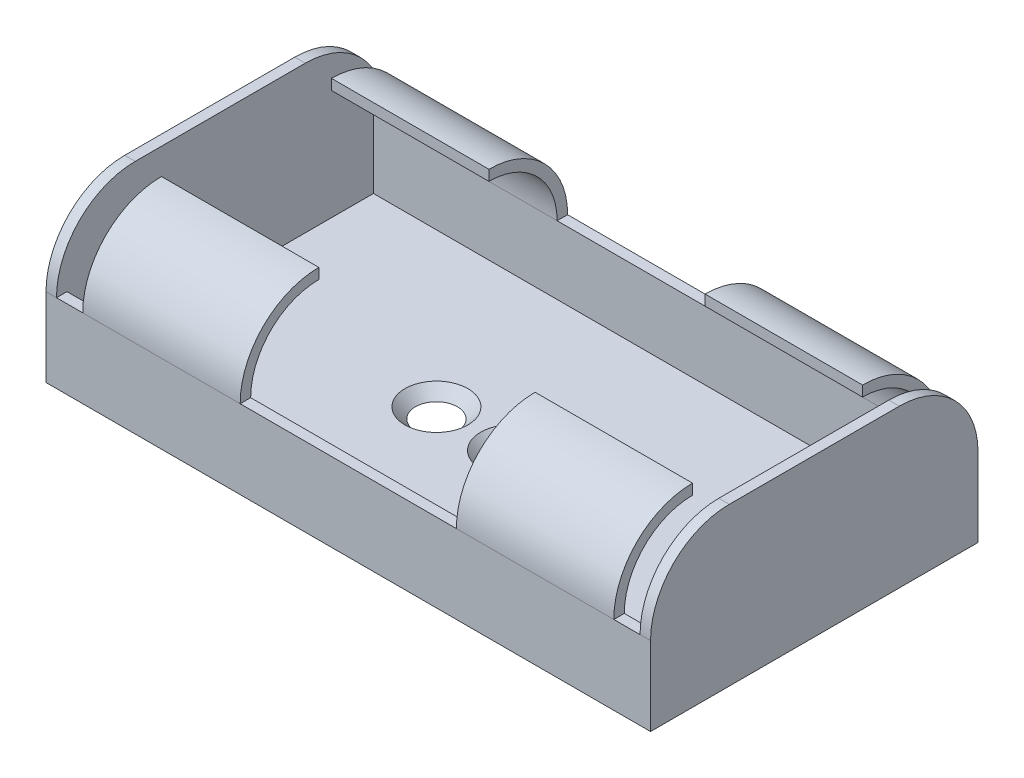
SolidWorks part; units mm, degrees
ref_plane "Front Plane" through (0, 0, 0) normal (0, 0, 1) x (1, 0, 0)
ref_plane "Top Plane" through (0, 0, 0) normal (0, 1, 0) x (1, 0, 0)
ref_plane "Right Plane" through (0, 0, 0) normal (1, 0, 0) x (0, 0, -1)
sketch "Sketch1" plane through (0, 0, 0) normal (0, 1, 0) x (1, 0, 0)
  line L1 (-28.8, 15.6) -> (28.8, 15.6)
  line L2 (-28.8, 15.6) -> (-28.8, -15.6)
  line L3 (-28.8, -15.6) -> (28.8, -15.6)
  line L4 (28.8, 15.6) -> (28.8, -15.6)
  line L5 (-28.8, 15.6) -> (28.8, -15.6) construction
  line L6 (-28.8, -15.6) -> (28.8, 15.6) construction
  point P0 (0, 0)
  dimension "D1" = 57.6
  dimension "D2" = 31.2
extrude "Boss-Extrude1" add sketch "Sketch1" along normal blind 15
fillet "Fillet1" radius 7.5 2 edges at (0, 15, -15.6) (0, 15, 15.6)
shell "Shell1" thickness 1 removed face at (0, 15, 0)
sketch "Sketch4" plane through (0, 0, 15.6) normal (0, 0, 1) x (1, 0, 0)
  line L0 (28.8, 7.5) -> (-28.8, 7.5) construction
  line L1 (-27.8, 15) -> (-25.3, 15)
  line L2 (-27.8, 15) -> (-27.8, 7.5)
  line L3 (-27.8, 7.5) -> (-25.3, 7.5)
  line L4 (-25.3, 15) -> (-25.3, 7.5)
  line L5 (-27.8, 15) -> (27.8, 15) construction
  line L6 (-10.3, 15) -> (10.3, 15)
  line L7 (-10.3, 15) -> (-10.3, 7.5)
  line L8 (-10.3, 7.5) -> (10.3, 7.5)
  line L10 (0, 0) -> (0, 7.5) construction
  line L11 (-28.8, 0) -> (28.8, 0) construction
  line L12 (10.3, 15) -> (10.3, 7.5)
  line L13 (25.3, 15) -> (25.3, 7.5)
  line L14 (27.8, 7.5) -> (25.3, 7.5)
  line L15 (27.8, 15) -> (27.8, 7.5)
  line L16 (27.8, 15) -> (25.3, 15)
  dimension "D1" = 2.5
  dimension "D2" = 15
extrude "Cut-Extrude1" cut sketch "Sketch4" against normal through all
sketch "Sketch5" plane through (0, 1, 0) normal (0, 1, 0) x (1, 0, 0)
  circle A0 centre (0, 0) radius 1.4
  circle A1 centre (7.2, 0) radius 1.4
  circle A2 centre (-7.2, 0) radius 1.4
  dimension "D1" = 2.8
  dimension "D2" = 7.2
  dimension "D3" = 7.2
extrude "Cut-Extrude2" cut sketch "Sketch5" against normal blind 15
hole_wizard "M3 Tapped Hole1" positions "Sketch6" profile "Sketch7" tap size "M3" standard "ISO"
sketch "Sketch6" plane through (0, 1, 31.4) normal (0, 1, 0) x (1, 0, 0)
  point P0 (7.2, 31.4)
  point P3 (0, 31.4)
  point P6 (-7.2, 31.4)
sketch "Sketch7" plane through (7.2, 1, 0) normal (1, 0, 0) x (0, 0, 1)
  line L0 (0, 0) -> (0, 16.7511)
  line L1 (0, 16.7511) -> (1.25, 16)
  line L2 (1.25, 16) -> (1.25, 1.75)
  line L3 (1.25, 1.75) -> (3, 0)
  line L4 (3, 0) -> (0, 0)
  line L5 (-1.25, 1.75) -> (-3, 0) construction
  line L6 (0, 16.7511) -> (-1.25, 16) construction
  line L7 (0, -6.35) -> (0, 107.95) construction
  dimension "Tap Drill Dia." = 2.5
  dimension "Tap Drill Depth" = 16
  dimension "Near C'Sink Dia." = 6
  dimension "Near C'Sink Angle" = 90
  dimension "Drill Angle" = 118
